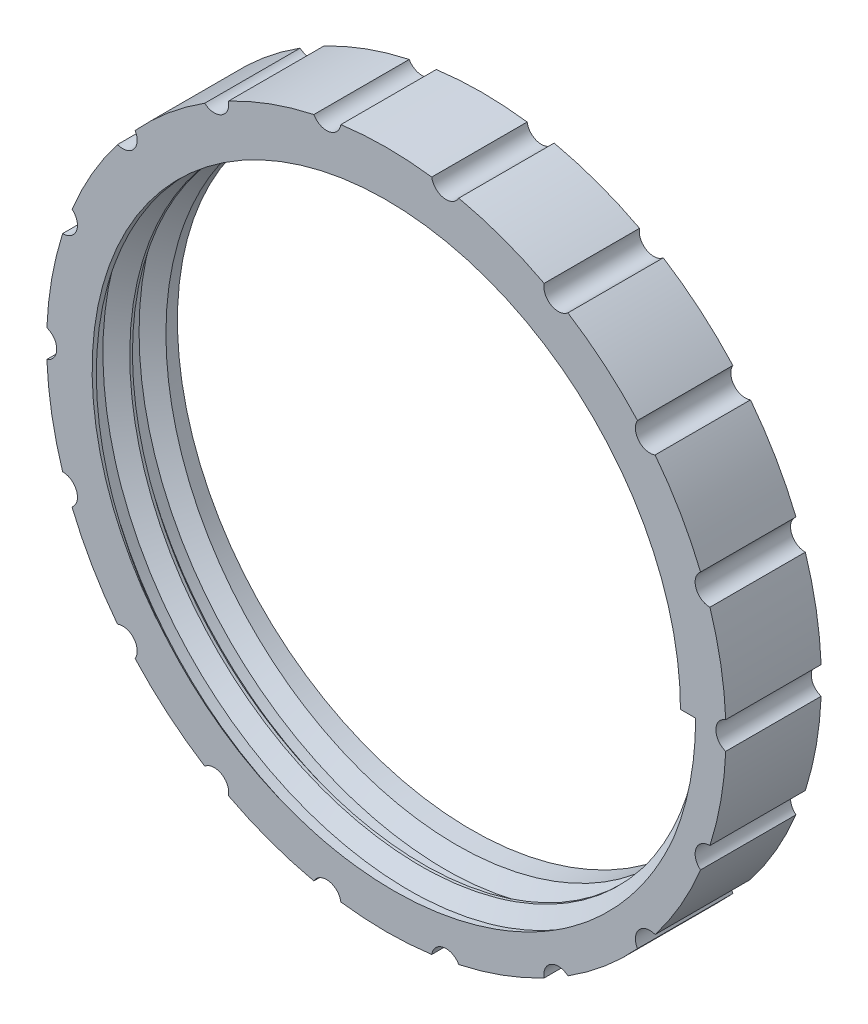
SolidWorks part; units mm, degrees
ref_plane "Front Plane" through (0, 0, 0) normal (0, 0, 1) x (1, 0, 0)
ref_plane "Top Plane" through (0, 0, 0) normal (0, 1, 0) x (1, 0, 0)
ref_plane "Right Plane" through (0, 0, 0) normal (1, 0, 0) x (0, 0, -1)
sketch "Sketch1" plane through (0, 0, 0) normal (0, 0, 1) x (1, 0, 0)
  circle A0 centre (0, 0) radius 23.5
  circle A1 centre (0, 0) radius 20.35
extrude "Grip_ring_D47" add sketch "Sketch1" along normal blind 6.6 from offset 0.2 offset against normal yes
ref_plane "Lower_female_D42_P2p5_start_plane" through (0, 0, 1.2) normal (0, 0, 1) x (1, 0, 0)
sketch "Sketch2" plane through (0, 0, 1.2) normal (0, 0, 1) x (1, 0, 0)
  circle A0 centre (0, 0) radius 19.9
curve "Lower_female_D42_P2p5_helix" pitch 2.5 height 5 radius 19.9 centre (0, 0, 1.2) axis (0, 0, 1) start towards (1, 0, 0)
sketch3d "3DSketch1"
  line L0 (20.1, 0, -0.15) -> (21.4, 0, 0.85)
  line L1 (21.4, 0, 0.85) -> (21.4, 0, 1.55)
  line L2 (21.4, 0, 1.55) -> (20.1, 0, 2.55)
  line L3 (20.1, 0, 2.55) -> (20.1, 0, -0.15)
sweep "Lower_female_D42_P2p5" cut profiles "3DSketch1" path "Lower_female_D42_P2p5_helix" align with end faces yes
sketch "Sketch3" plane through (0, 0, 0) normal (0, 0, 1) x (1, 0, 0)
  circle A0 centre (23.8, 0) radius 1
  circle A1 centre (22.3647, 8.1401) radius 1
  circle A2 centre (18.2319, 15.2983) radius 1
  circle A3 centre (11.9, 20.6114) radius 1
  circle A4 centre (4.1328, 23.4384) radius 1
  circle A5 centre (-4.1328, 23.4384) radius 1
  circle A6 centre (-11.9, 20.6114) radius 1
  circle A7 centre (-18.2319, 15.2983) radius 1
  circle A8 centre (-22.3647, 8.1401) radius 1
  circle A9 centre (-23.8, 0) radius 1
  circle A10 centre (-22.3647, -8.1401) radius 1
  circle A11 centre (-18.2319, -15.2983) radius 1
  circle A12 centre (-11.9, -20.6114) radius 1
  circle A13 centre (-4.1328, -23.4384) radius 1
  circle A14 centre (4.1328, -23.4384) radius 1
  circle A15 centre (11.9, -20.6114) radius 1
  circle A16 centre (18.2319, -15.2983) radius 1
  circle A17 centre (22.3647, -8.1401) radius 1
extrude "Grip_flutes" cut sketch "Sketch3" along normal blind 6.6 from offset 0.2 offset against normal yes
sketch "Sketch4" plane through (0, 0, 0) normal (0, 0, 1) x (1, 0, 0)
  circle A0 centre (0, 0) radius 21.4
extrude "Hand_start_thread_entry_relief" cut sketch "Sketch4" along normal blind 0.71 from offset 0.21 offset against normal yes
